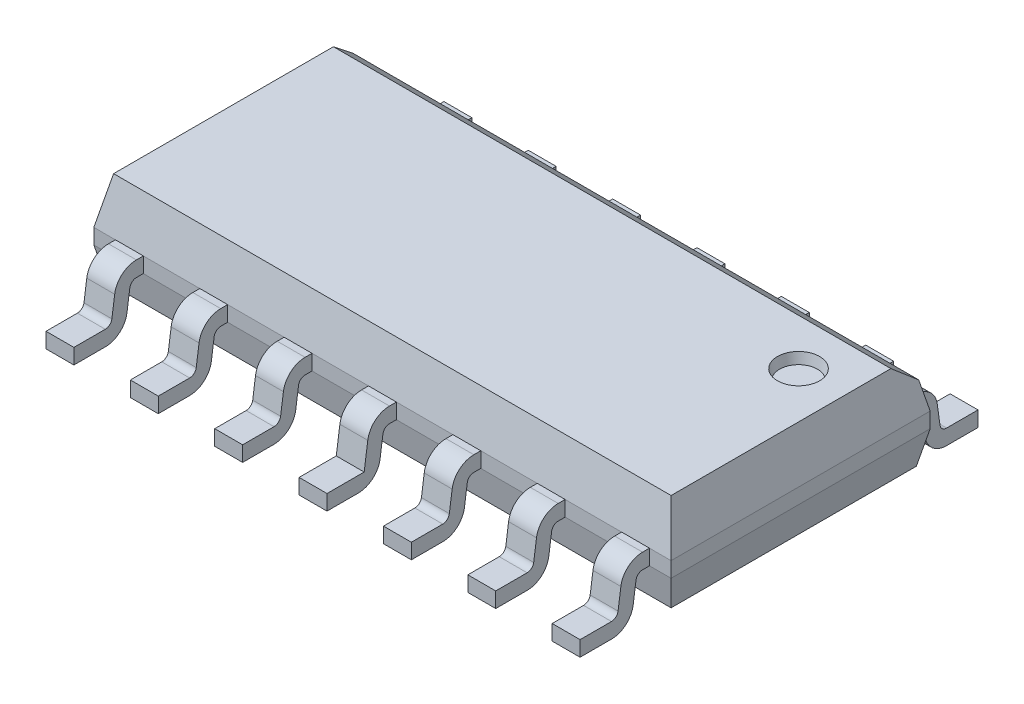
SolidWorks part; units mm, degrees
note: '?' marks a value the reader was unsure of.
ref_plane "Front Plane" through (0, 0, 0) normal (0, 0, 1) x (1, 0, 0)
ref_plane "Top Plane" through (0, 0, 0) normal (0, 1, 0) x (1, 0, 0)
ref_plane "Right Plane" through (0, 0, 0) normal (1, 0, 0) x (0, 0, -1)
ref_axis "Axis1" through (4.7795, 0, 0) along (-1, 0, 0)?
sketch "Sketch1" plane through (0, 0, 0) normal (0, 1, 0) x (1, 0, 0)
  line L1 (-4.345, 1.95) -> (4.345, 1.95)
  line L2 (-4.345, 1.95) -> (-4.345, -1.95)
  line L3 (-4.345, -1.95) -> (4.345, -1.95)
  line L4 (4.345, 1.95) -> (4.345, -1.95)
  dimension "D1" = 8.69
  dimension "D2" = 3.9
  dimension "D3" = 4.345
  dimension "D4" = 1.95
extrude "Extrude1" add sketch "Sketch1" along normal blind 0.7 draft 12 and the other way blind 0.23
sketch "Sketch2" plane through (0, -0.23, 0) normal (0, -1, 0) x (1, 0, 0)
  line L4 (-4.345, 1.95) -> (-4.345, -1.95)
  line L5 (-4.345, -1.95) -> (4.345, -1.95)
  line L6 (4.345, -1.95) -> (4.345, 1.95)
  line L7 (4.345, 1.95) -> (-4.345, 1.95)
  line L8 (-4.345, 1.95) -> (-4.345, -1.95)
  line L9 (-4.345, -1.95) -> (4.345, -1.95)
  line L10 (4.345, -1.95) -> (4.345, 1.95)
  line L11 (4.345, 1.95) -> (-4.345, 1.95)
  dimension "D1" = 0
extrude "Extrude2" add sketch "Sketch2" along normal blind 0.49 draft 12
chamfer "Chamfer1" distance 0.3 angle 38.5 1 edges at (0, 0.7, -1.8012)
sketch "Sketch3" plane through (0, 0.7, 0) normal (0, 1, 0) x (-1, 0, 0)
  circle A0 centre (-3.5015, -0.8119) radius 0.3175
extrude "Cut-Extrude1" cut sketch "Sketch3" against normal blind 0.15 draft 12
sketch "Sketch4" plane through (0, 0, 0) normal (1, 0, 0) x (0, 0, -1)
  line L0 (1.95, -0.23) -> (-1.95, -0.23) construction
  line L1 (1.95, 0) -> (-1.95, 0) construction
  line L2 (1.95, -0.23) -> (-1.95, -0.23)
  line L3 (1.95, 0) -> (-1.95, 0)
  line L4 (-1.8458, -0.72) -> (1.8458, -0.72) construction
  line L5 (2.995, -0.67) -> (2.4354, -0.67)
  line L6 (2.995, -0.67) -> (2.995, -0.9)
  line L7 (2.995, -0.9) -> (2.2355, -0.9)
  line L8 (2.155, -0.67) -> (2.155, -0.9) construction
  line L9 (-2.155, -0.67) -> (-2.4354, -0.67) construction
  line L10 (-2.155, -0.67) -> (-2.155, -0.9) construction
  line L11 (-2.155, -0.9) -> (-2.2355, -0.9) construction
  line L12 (-2.995, -0.67) -> (-2.995, -0.9)
  line L13 (1.95, 0) -> (2.3413, 0)
  line L14 (2.6703, 0) -> (2.6703, -0.23) construction
  line L15 (2.6703, -0.23) -> (2.1413, -0.23) construction
  line L16 (-1.95, 0) -> (-2.3413, 0)
  line L17 (-2.6934, 0) -> (-2.6934, -0.23) construction
  line L18 (-2.6934, -0.23) -> (-2.1413, -0.23) construction
  line L19 (2.3413, 0) -> (2.6703, 0) construction
  line L20 (2.4354, -0.67) -> (2.3413, 0)
  line L21 (2.2355, -0.9) -> (2.1413, -0.23)
  line L22 (2.1413, -0.23) -> (1.95, -0.23)
  line L23 (2.2355, -0.9) -> (2.155, -0.9) construction
  line L24 (2.4354, -0.67) -> (2.155, -0.67) construction
  line L25 (0, -1.1578) -> (0, -1.9582) construction
  line L26 (-2.2355, -0.9) -> (-2.1413, -0.23)
  line L27 (-2.4354, -0.67) -> (-2.3413, 0)
  line L28 (-2.1413, -0.23) -> (-1.95, -0.23)
  line L29 (-2.3413, 0) -> (-2.6934, 0) construction
  line L30 (-2.4354, -0.67) -> (-2.995, -0.67)
  line L31 (-2.2355, -0.9) -> (-2.995, -0.9)
  dimension "D1" = 0.84
  dimension "D2" = 5.99
  dimension "D3" = 2.995
  dimension "D4" = 0.18
  dimension "D5" = 0.23
  dimension "D6" = 0.23
extrude "Extrude3" add sketch "Sketch4" along normal blind 0.21 and the other way blind 0.21
pattern_linear "LPattern3" count 4 spacing 1.27 along (1, 0, 0) count 4 spacing 1.27 along (-1, 0, 0) of "Extrude3"
fillet "Fillet1" radius 0.1 27 edges at (0, -0.23, 2.1413) (0, -0.67, -2.4354) (0, -0.23, -2.1413) (-3.81, -0.67, 2.4354) (-2.54, -0.67, 2.4354) (-1.27, -0.67, 2.4354) (1.27, -0.67, 2.4354) (2.54, -0.67, 2.4354) (3.81, -0.67, 2.4354) (3.81, -0.67, -2.4354) (2.54, -0.67, -2.4354) (1.27, -0.67, -2.4354) (-1.27, -0.67, -2.4354) (-2.54, -0.67, -2.4354) (-3.81, -0.67, -2.4354) (-3.81, -0.23, 2.1413) (-2.54, -0.23, 2.1413) (-1.27, -0.23, 2.1413) (1.27, -0.23, 2.1413) (2.54, -0.23, 2.1413) (3.81, -0.23, 2.1413) (-3.81, -0.23, -2.1413) (-2.54, -0.23, -2.1413) (-1.27, -0.23, -2.1413) (3.81, -0.23, -2.1413) (2.54, -0.23, -2.1413) (1.27, -0.23, -2.1413)
fillet "Fillet2" radius 0.33 28 edges at (-1.27, 0, -2.3413) (-1.27, -0.9, -2.2355) (-1.27, 0, 2.3413) (-1.27, -0.9, 2.2355) (-2.54, 0, -2.3413) (-2.54, -0.9, -2.2355) (-2.54, 0, 2.3413) (-2.54, -0.9, 2.2355) (-3.81, 0, -2.3413) (-3.81, -0.9, -2.2355) (-3.81, 0, 2.3413) (-3.81, -0.9, 2.2355) (1.27, 0, -2.3413) (1.27, -0.9, -2.2355) (1.27, 0, 2.3413) (1.27, -0.9, 2.2355) (2.54, 0, -2.3413) (2.54, -0.9, -2.2355) (2.54, 0, 2.3413) (2.54, -0.9, 2.2355) (3.81, 0, -2.3413) (3.81, -0.9, -2.2355) (3.81, 0, 2.3413) (3.81, -0.9, 2.2355) (0, 0, -2.3413) (0, -0.9, -2.2355) (0, 0, 2.3413) (0, -0.9, 2.2355)
ref_plane "Plane1" through (0, -0.9, 0) normal (0, 1, 0) x (-1, 0, 0)
sketch "Component_Outline" plane through (0, -0.9, 0) normal (0, 1, 0) x (-1, 0, 0)
  line L0 (4.345, -1.95) -> (4.02, -1.95)
  line L1 (4.02, -1.95) -> (4.02, -2.995)
  line L2 (4.02, -2.995) -> (3.6, -2.995)
  line L3 (3.6, -2.995) -> (3.6, -1.95)
  line L4 (3.6, -1.95) -> (2.75, -1.95)
  line L5 (2.75, -1.95) -> (2.75, -2.995)
  line L6 (2.75, -2.995) -> (2.33, -2.995)
  line L7 (2.33, -2.995) -> (2.33, -1.95)
  line L8 (2.33, -1.95) -> (1.48, -1.95)
  line L9 (1.48, -1.95) -> (1.48, -2.995)
  line L10 (1.48, -2.995) -> (1.06, -2.995)
  line L11 (1.06, -2.995) -> (1.06, -1.95)
  line L12 (1.06, -1.95) -> (0.21, -1.95)
  line L13 (0.21, -1.95) -> (0.21, -2.995)
  line L14 (0.21, -2.995) -> (-0.21, -2.995)
  line L15 (-0.21, -2.995) -> (-0.21, -1.95)
  line L16 (-0.21, -1.95) -> (-1.06, -1.95)
  line L17 (-1.06, -1.95) -> (-1.06, -2.995)
  line L18 (-1.06, -2.995) -> (-1.48, -2.995)
  line L19 (-1.48, -2.995) -> (-1.48, -1.95)
  line L20 (-1.48, -1.95) -> (-2.33, -1.95)
  line L21 (-2.33, -1.95) -> (-2.33, -2.995)
  line L22 (-2.33, -2.995) -> (-2.75, -2.995)
  line L23 (-2.75, -2.995) -> (-2.75, -1.95)
  line L24 (-2.75, -1.95) -> (-3.6, -1.95)
  line L25 (-3.6, -1.95) -> (-3.6, -2.995)
  line L26 (-3.6, -2.995) -> (-4.02, -2.995)
  line L27 (-4.02, -2.995) -> (-4.02, -1.95)
  line L28 (-4.02, -1.95) -> (-4.345, -1.95)
  line L29 (4.345, 0) -> (-4.345, 0) construction
  line L30 (4.345, -1.95) -> (4.345, 1.95) construction
  line L31 (-4.345, 1.95) -> (-4.345, -1.95) construction
  line L32 (-4.02, 1.95) -> (-4.345, 1.95)
  line L33 (-4.02, 2.995) -> (-4.02, 1.95)
  line L34 (-3.6, 2.995) -> (-4.02, 2.995)
  line L35 (-3.6, 1.95) -> (-3.6, 2.995)
  line L36 (-2.75, 1.95) -> (-3.6, 1.95)
  line L37 (-2.75, 2.995) -> (-2.75, 1.95)
  line L38 (-2.33, 2.995) -> (-2.75, 2.995)
  line L39 (-2.33, 1.95) -> (-2.33, 2.995)
  line L40 (-1.48, 1.95) -> (-2.33, 1.95)
  line L41 (-1.48, 2.995) -> (-1.48, 1.95)
  line L42 (-1.06, 2.995) -> (-1.48, 2.995)
  line L43 (-1.06, 1.95) -> (-1.06, 2.995)
  line L44 (-0.21, 1.95) -> (-1.06, 1.95)
  line L45 (-0.21, 2.995) -> (-0.21, 1.95)
  line L46 (0.21, 2.995) -> (-0.21, 2.995)
  line L47 (0.21, 1.95) -> (0.21, 2.995)
  line L48 (1.06, 1.95) -> (0.21, 1.95)
  line L49 (1.06, 2.995) -> (1.06, 1.95)
  line L50 (1.48, 2.995) -> (1.06, 2.995)
  line L51 (1.48, 1.95) -> (1.48, 2.995)
  line L52 (2.33, 1.95) -> (1.48, 1.95)
  line L53 (2.33, 2.995) -> (2.33, 1.95)
  line L54 (2.75, 2.995) -> (2.33, 2.995)
  line L55 (2.75, 1.95) -> (2.75, 2.995)
  line L56 (3.6, 1.95) -> (2.75, 1.95)
  line L57 (3.6, 2.995) -> (3.6, 1.95)
  line L58 (4.02, 2.995) -> (3.6, 2.995)
  line L59 (4.02, 1.95) -> (4.02, 2.995)
  line L60 (4.345, 1.95) -> (4.02, 1.95)
  line L61 (-4.345, -1.95) -> (-4.345, 1.95)
  line L62 (4.345, -1.95) -> (4.345, 1.95)
